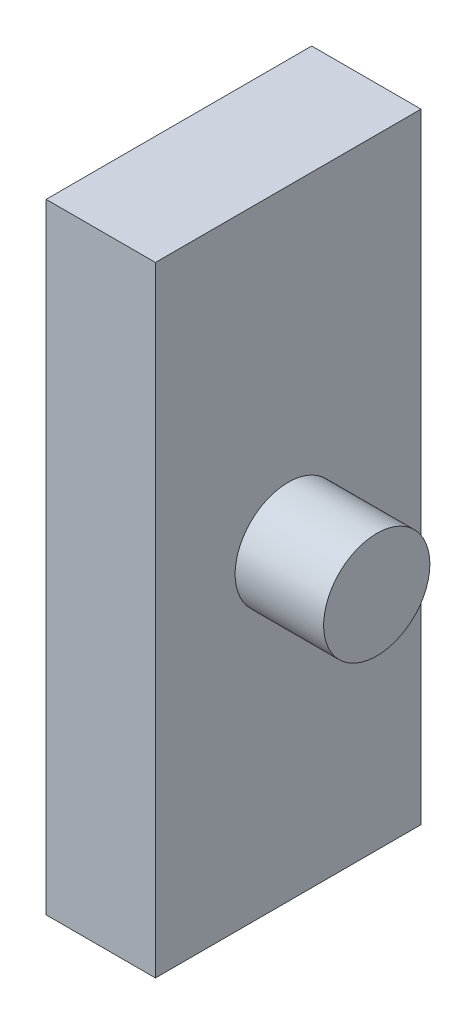
SolidWorks part; units mm, degrees
ref_plane "Front Plane" through (0, 0, 0) normal (0, 0, 1) x (1, 0, 0)
ref_plane "Top Plane" through (0, 0, 0) normal (0, 1, 0) x (1, 0, 0)
ref_plane "Right Plane" through (0, 0, 0) normal (1, 0, 0) x (0, 0, -1)
sketch "Sketch1" plane through (0, 0, 0) normal (1, 0, 0) x (0, 0, -1)
  line L0 (5.8125, 17.5) -> (9.1875, 17.5) construction
  line L1 (5.8125, 26) -> (9.1875, 26)
  line L2 (5.8125, 26) -> (5.8125, 9)
  line L3 (5.8125, 9) -> (9.1875, 9)
  line L4 (9.1875, 26) -> (9.1875, 9)
  line L5 (7.5, 26) -> (7.5, 9) construction
  line L6 (7.5, 35) -> (7.5, 0) construction
  line L15 (0, 35) -> (15, 35)
  line L16 (0, 35) -> (0, 0)
  line L17 (0, 0) -> (15, 0)
  line L18 (15, 35) -> (15, 0)
  line L19 (0, 17.5) -> (15, 17.5) construction
  dimension "D2" = 3.375
  dimension "D3" = 17
  dimension "D4" = 15
  dimension "D5" = 35
extrude "Boss-Extrude1" add sketch "Sketch1" along normal blind 4.175
sketch "Sketch2" plane through (4.175, 0, 0) normal (1, 0, 0) x (0, 0, -1)
  line L1 (0, 35) -> (15, 35)
  line L2 (0, 35) -> (0, 0)
  line L3 (0, 0) -> (15, 0)
  line L4 (15, 35) -> (15, 0)
extrude "Boss-Extrude2" add sketch "Sketch2" along normal blind 2
sketch "Sketch3" plane through (6.175, 0, 0) normal (1, 0, 0) x (0, 0, -1)
  line L0 (7.5, 35) -> (7.5, 0) construction
  line L1 (15, 35) -> (0, 35) construction
  line L2 (0, 0) -> (15, 0) construction
  line L3 (0, 17.5) -> (15, 17.5) construction
  line L4 (0, 35) -> (0, 0) construction
  line L5 (15, 0) -> (15, 35) construction
  circle A0 centre (7.5, 17.5) radius 3
  dimension "D1" = 6
extrude "Boss-Extrude3" add sketch "Sketch3" along normal blind 5
